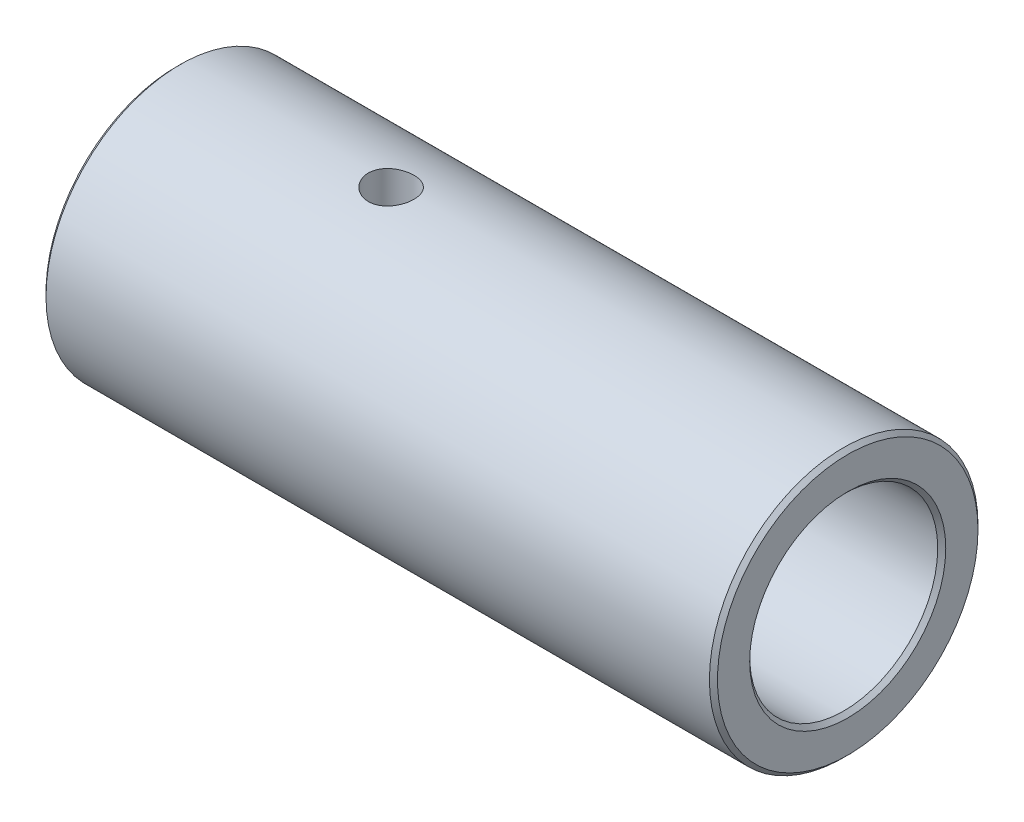
SolidWorks part; units mm, degrees
material "20"
ref_plane "前视基准面" through (0, 0, 0) normal (0, 0, 1) x (1, 0, 0)
ref_plane "上视基准面" through (0, 0, 0) normal (0, 1, 0) x (1, 0, 0)
ref_plane "右视基准面" through (0, 0, 0) normal (1, 0, 0) x (0, 0, -1)
sketch "草图1" plane through (0, 0, 0) normal (1, 0, 0) x (0, 0, -1)
  circle A0 centre (0, 0) radius 50
  circle A1 centre (0, 0) radius 35
  dimension "D1" = 100
  dimension "D2" = 70
extrude "凸台-拉伸1" add sketch "草图1" along normal blind 250
sketch "草图2" plane through (0, 0, 0) normal (0, 1, 0) x (1, 0, 0)
  line L1 (0, 50) -> (0, -50) construction
  circle A1 centre (80, 0) radius 8.5
  dimension "D1" = 17
  dimension "D3" = 80
extrude "切除-拉伸1" cut sketch "草图2" against normal mid plane 860
chamfer "倒角1" distance 1.5 angle 45 4 edges at (0, 0, -50) (250, 0, -50) (0, 0, -35) (250, 0, -35)
ref_axis "基准轴1" through (248.5, 0, 0) along (-1, 0, 0)
